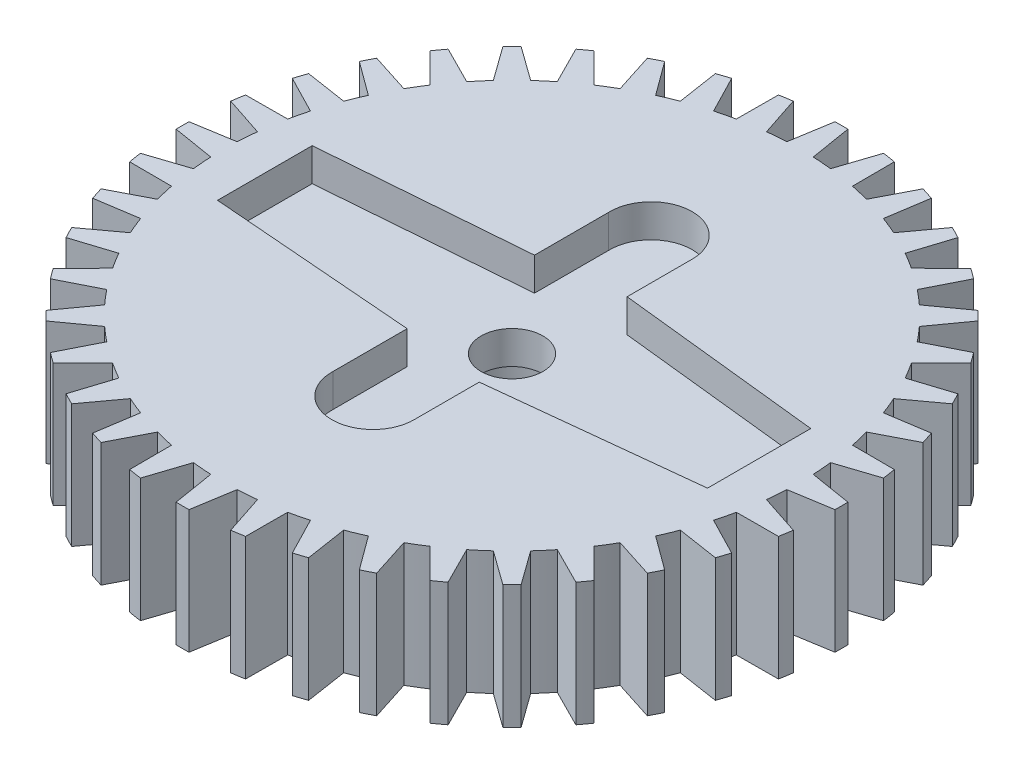
SolidWorks part; units mm, degrees
material "PBT General Purpose"
ref_plane "Front Plane" through (0, 0, 0) normal (0, 0, 1) x (1, 0, 0)
ref_plane "Top Plane" through (0, 0, 0) normal (0, 1, 0) x (1, 0, 0)
ref_plane "Right Plane" through (0, 0, 0) normal (1, 0, 0) x (0, 0, -1)
sketch "Sketch1" plane through (0, 0, 0) normal (0, 1, 0) x (1, 0, 0)
  circle A0 centre (0, 0) radius 1.5
  circle A1 centre (0, 0) radius 16
  dimension "D1" = 3
  dimension "D2" = 32
extrude "Boss-Extrude1" add sketch "Sketch1" along normal blind 6
sketch "Sketch2" plane through (0, 6, 0) normal (0, 1, 0) x (1, 0, 0)
  line L0 (0, 0) -> (0, 15.5) construction
  line L1 (0, 0) -> (-0.3141, 15.9969) construction
  line L2 (0, 0) -> (-0.6412, 13.9853) construction
  line L3 (0, 0) -> (-1.0984, 13.9568) construction
  line L4 (-0.6412, 13.9853) -> (-0.3141, 15.9969)
  line L5 (0.6412, 13.9853) -> (0.3141, 15.9969)
  line L6 (-1.0984, 13.9568) -> (-1.346, 17.1025)
  line L7 (-1.346, 17.1025) -> (1.346, 17.1025)
  line L8 (1.346, 17.1025) -> (1.0984, 13.9568)
  circle A0 centre (0, 0) radius 16 construction
  arc A1 (0.3141, 15.9969) -> (-0.3141, 15.9969) centre (0, 0) ccw
  arc A3 (-0.6412, 13.9853) -> (-1.0984, 13.9568) centre (0, 0) ccw
  arc A4 (0.6412, 13.9853) -> (1.0984, 13.9568) centre (0, 0) cw
  dimension "D4" = 14
  dimension "D1" = 1.125
  dimension "D2" = 1.5
  dimension "D3" = 1.875
extrude "Cut-Extrude1" cut sketch "Sketch2" against normal up to next (6 mm away)
pattern_circular "CirPattern1" count 40 over 360 about axis through (0, 6, 0) along (0, -1, 0) of "Cut-Extrude1" reverse direction yes
sketch "Sketch3" plane through (0, 6, 0) normal (0, 1, 0) x (1, 0, 0)
  line L0 (15.75, 0) -> (-15.75, 0) construction
  line L1 (0, -6.75) -> (0, 6.75) construction
  line L2 (-1.8988, 6.6833) -> (-1.8988, 3) construction
  line L3 (1.8988, 6.6833) -> (1.8988, 3.5) construction
  line L4 (-15.75, 1.9) -> (-1.8988, 3) construction
  line L5 (15.7506, 2) -> (1.8988, 3.5) construction
  line L6 (15.7506, -2) -> (1.8988, -3.5) construction
  line L7 (1.8988, -6.6833) -> (1.8988, -3.5) construction
  line L8 (-1.8988, -6.6833) -> (-1.8988, -3) construction
  line L9 (-15.75, -1.9) -> (-1.8988, -3) construction
  line L10 (-1.9988, 6.6816) -> (-1.9988, 3.0924)
  line L11 (-15.754, 2) -> (-1.9988, 3.0924)
  line L12 (-15.754, -2) -> (-1.9988, -3.0924)
  line L13 (-1.9988, -6.6816) -> (-1.9988, -3.0924)
  line L14 (1.9988, -6.6816) -> (1.9988, -3.5898)
  line L15 (15.7561, -2.1) -> (1.9988, -3.5898)
  line L16 (15.7561, 2.1) -> (1.9988, 3.5898)
  line L17 (1.9988, 6.6816) -> (1.9988, 3.5898)
  line L18 (-12, 2.2981) -> (-12, -2.2981)
  line L19 (12, 2.5067) -> (12, -2.5067)
  circle A0 centre (0, 0) radius 1.25
  arc A1 (-1.8988, 6.6833) -> (1.8988, 6.6833) centre (0, 6.75) cw construction
  arc A2 (-15.75, 1.9) -> (-15.75, -1.9) centre (-15.75, 0) ccw construction
  arc A3 (15.7506, 2) -> (15.7506, -2) centre (15.75, 0) cw construction
  arc A4 (-1.8988, -6.6833) -> (1.8988, -6.6833) centre (0, -6.75) ccw construction
  arc A5 (-15.754, 2) -> (-15.754, -2) centre (-15.75, 0) ccw
  arc A6 (-1.9988, -6.6816) -> (1.9988, -6.6816) centre (0, -6.75) ccw
  arc A7 (15.7561, 2.1) -> (15.7561, -2.1) centre (15.75, 0) cw
  arc A8 (-1.9988, 6.6816) -> (1.9988, 6.6816) centre (0, 6.75) cw
  point P5 (0, 0)
  point P8 (0, 0)
  dimension "D1" = 2.5
  dimension "D4" = 1.9
  dimension "D5" = 1.9
  dimension "D11" = 2
  dimension "D2" = 13.5
  dimension "D3" = 31.5
  dimension "D6" = 1.1
  dimension "D8" = 6
  dimension "D9" = 7
  dimension "D10" = 3.5
  dimension "D12" = 12
  dimension "D13" = 12
  dimension "D7" = 0.1
extrude "Cut-Extrude2" cut sketch "Sketch3" against normal blind 1.6 contours A8 L10 L11 A5 L12 L13 A6 L14 L15 A7 L16 L17 A4 L8 L9 A2 L4 L2 A1 L3 L5 A3 L6 L7 | L8 A4 L7 L6 A3 L5 L3 A1 L2 L4 A2 L9 A0 region at (0, 6, -8.453)
sketch "Sketch4" plane through (0, 0, 0) normal (0, -1, 0) x (1, 0, 0)
  circle A0 centre (0, 0) radius 2.6
  dimension "D1" = 5.2
extrude "Cut-Extrude3" cut sketch "Sketch4" against normal offset from surface (2.8 mm away) 1.6 up to face at (0, 4.4, 1.5)
equation "\"num_teeth\"= 40"
equation "\"D1@Sketch2\"=(1.5/6)*(360 / \"num_teeth\")*0.5"
equation "\"D2@Sketch2\"=(2/6)*(360 / \"num_teeth\")*0.5"
equation "\"D3@Sketch2\"=(2.5/6)*(360 / \"num_teeth\")*0.5"
equation "\"D1@CirPattern1\"=\"num_teeth\""
equation "\"diameter\"= 30mm"
equation "\"D2@Sketch1\"=\"diameter\" + 2"
equation "\"D4@Sketch2\"=(\"diameter\" / 2) - 1"
